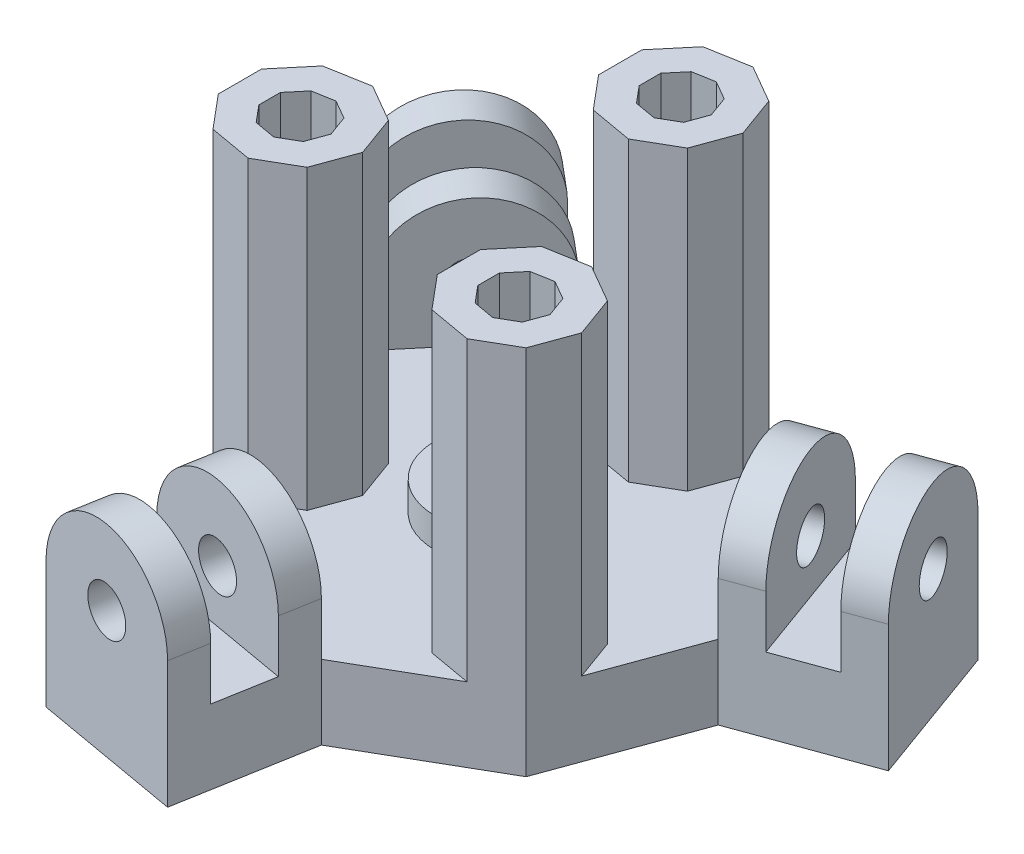
SolidWorks part; units mm, degrees
ref_plane "Front Plane" through (0, 0, 0) normal (0, 0, 1) x (1, 0, 0)
ref_plane "Top Plane" through (0, 0, 0) normal (0, 1, 0) x (1, 0, 0)
ref_plane "Right Plane" through (0, 0, 0) normal (1, 0, 0) x (0, 0, -1)
sketch "Sketch1" plane through (0, 0, 0) normal (0, 1, 0) x (1, 0, 0)
  line L0 (-17.5976, -6.405) -> (-9.3635, -16.2181)
  line L1 (14.3457, -12.0375) -> (18.727, 0)
  line L2 (18.727, 0) -> (14.3457, 12.0375)
  line L3 (14.3457, 12.0375) -> (3.2519, 18.4425)
  line L4 (3.2519, 18.4425) -> (-9.3635, 16.2181)
  line L5 (-9.3635, 16.2181) -> (-17.5976, 6.405)
  line L6 (-17.5976, 6.405) -> (-17.5976, -6.405)
  line L7 (-9.3635, -16.2181) -> (3.2519, -18.4425)
  line L8 (3.2519, -18.4425) -> (14.3457, -12.0375)
  line L9 (14.3457, 12.0375) -> (18.727, 0)
  line L10 (14.3457, 12.0375) -> (25.0112, 15.9194)
  line L11 (18.727, 0) -> (29.3925, 3.8819)
  line L12 (25.0112, 15.9194) -> (29.3925, 3.8819)
  line L13 (3.2519, -18.4425) -> (-9.3635, -16.2181)
  line L14 (3.2519, -18.4425) -> (1.281, -29.6201)
  line L15 (-9.3635, -16.2181) -> (-11.3344, -27.3956)
  line L16 (1.281, -29.6201) -> (-11.3344, -27.3956)
  line L17 (-17.5976, 6.405) -> (-9.3635, 16.2181)
  line L18 (-17.5976, 6.405) -> (-26.2922, 13.7007)
  line L19 (-9.3635, 16.2181) -> (-18.0581, 23.5137)
  line L20 (-26.2922, 13.7007) -> (-18.0581, 23.5137)
  circle A0 centre (0, 0) radius 17.5976 construction
  circle A1 centre (0, 0) radius 4.1
  dimension "D1" = 35.1953
  dimension "D2" = 8.2
  dimension "D3" = 11.35
extrude "Boss-Extrude1" add sketch "Sketch1" along normal blind 6.35 contours L16 L14 L7 L15 | L7 L8 L1 L2 L3 L4 L5 L6 L0 A1 | L12 L10 L2 L11 | L20 L18 L5 L19 region at (-17.08, 0, 0) region at (-4.0413, 0, 22.9191) region at (-17.8279, 0, -14.9594) region at (21.8691, 0, -7.9597)
ref_plane "Plane1" through (-5.0267, 0, 28.5079) normal (0.1736, 0, -0.9848) x (-0.9848, 0, -0.1736)
sketch "Sketch4" plane through (-5.0267, 0, 28.5079) normal (0.1736, 0, -0.9848) x (-0.9848, 0, -0.1736)
  line L0 (-6.405, 6.35) -> (-6.405, 10.85)
  line L1 (6.405, 6.35) -> (6.405, 10.85)
  line L2 (-6.405, 6.35) -> (6.405, 6.35)
  arc A0 (6.405, 10.85) -> (-6.405, 10.85) centre (0, 10.85) ccw
  circle A1 centre (0, 10.85) radius 2
  dimension "D2" = 4
  dimension "D1" = 4.5
extrude "Boss-Extrude2" add sketch "Sketch4" along normal blind 3.18
ref_plane "Plane2" through (-3.0558, 0, 17.3303) normal (0.1736, 0, -0.9848) x (-0.9848, 0, -0.1736)
sketch "Sketch6" plane through (-3.0558, 0, 17.3303) normal (0.1736, 0, -0.9848) x (-0.9848, 0, -0.1736)
  line L0 (-6.405, 6.35) -> (-6.405, 10.85)
  line L1 (6.405, 6.35) -> (6.405, 10.85)
  line L2 (-6.405, 6.35) -> (6.405, 6.35)
  arc A0 (6.405, 10.85) -> (-6.405, 10.85) centre (0, 10.85) ccw
  circle A1 centre (0, 10.85) radius 2
  dimension "D2" = 4
  dimension "D1" = 4.5
extrude "Boss-Extrude4" add sketch "Sketch6" against normal blind 3.175
ref_plane "Plane3" through (27.2019, 0, -9.9007) normal (-0.9397, 0, 0.342) x (0.342, 0, 0.9397)
sketch "Sketch8" plane through (27.2019, 0, -9.9007) normal (-0.9397, 0, 0.342) x (0.342, 0, 0.9397)
  line L0 (-6.405, 10.85) -> (-6.405, 6.35)
  line L1 (-6.405, 6.35) -> (6.405, 6.35)
  line L2 (6.405, 6.35) -> (6.405, 10.85)
  arc A0 (6.405, 10.85) -> (-6.405, 10.85) centre (0, 10.85) ccw
  circle A1 centre (0, 10.85) radius 2
  dimension "D2" = 4
  dimension "D1" = 4.5
extrude "Boss-Extrude5" add sketch "Sketch8" along normal blind 3.175
ref_plane "Plane4" through (16.5364, 0, -6.0187) normal (-0.9397, 0, 0.342) x (0.342, 0, 0.9397)
sketch "Sketch9" plane through (16.5364, 0, -6.0187) normal (-0.9397, 0, 0.342) x (0.342, 0, 0.9397)
  line L0 (-6.405, 6.35) -> (-6.405, 10.85)
  line L1 (-6.405, 6.35) -> (6.405, 6.35)
  line L2 (6.405, 6.35) -> (6.405, 10.85)
  arc A0 (-6.405, 10.85) -> (6.405, 10.85) centre (0, 10.85) cw
  circle A1 centre (0, 10.85) radius 2
  dimension "D2" = 4
  dimension "D1" = 4.5
extrude "Boss-Extrude6" add sketch "Sketch9" against normal blind 3.175
ref_plane "Plane5" through (-22.1752, 0, -18.6072) normal (0.766, 0, 0.6428) x (0.6428, 0, -0.766)
sketch "Sketch10" plane through (-22.1752, 0, -18.6072) normal (0.766, 0, 0.6428) x (0.6428, 0, -0.766)
  line L0 (-6.405, 10.85) -> (-6.405, 6.35)
  line L1 (-6.405, 6.35) -> (6.405, 6.35)
  line L2 (6.405, 6.35) -> (6.405, 10.85)
  arc A0 (6.405, 10.85) -> (-6.405, 10.85) centre (0, 10.85) ccw
  circle A1 centre (0, 10.85) radius 2
  dimension "D2" = 4
  dimension "D1" = 4.5
extrude "Boss-Extrude7" add sketch "Sketch10" along normal blind 3.175
ref_plane "Plane6" through (-13.4806, 0, -11.3115) normal (0.766, 0, 0.6428) x (0.6428, 0, -0.766)
sketch "Sketch11" plane through (-13.4806, 0, -11.3115) normal (0.766, 0, 0.6428) x (0.6428, 0, -0.766)
  line L0 (-6.405, 10.85) -> (-6.405, 6.35)
  line L1 (-6.405, 6.35) -> (6.405, 6.35)
  line L2 (6.405, 6.35) -> (6.405, 10.85)
  arc A0 (6.405, 10.85) -> (-6.405, 10.85) centre (0, 10.85) ccw
  circle A1 centre (0, 10.85) radius 2
  dimension "D2" = 4
  dimension "D1" = 4.5
extrude "Boss-Extrude8" add sketch "Sketch11" against normal blind 3.175
ref_plane "Plane7" through (0, 6.35, 0) normal (0, 1, 0) x (1, 0, 0)
sketch "Sketch12" plane through (0, 6.35, 0) normal (0, 1, 0) x (1, 0, 0)
  line L9 (14.3457, -12.0375) -> (18.727, 0) construction
  line L29 (14.3457, -12.0375) -> (15.6105, -8.5626)
  line L38 (15.6105, -8.5626) -> (14.3457, -5.0876)
  line L48 (6.4544, 9.6437) -> (7.7192, 13.1186)
  line L49 (3.2519, 18.4425) -> (-0.3898, 17.8004)
  line L50 (-0.3898, 17.8004) -> (-2.7668, 14.9676)
  line L51 (-2.7668, 14.9676) -> (-2.7668, 11.2696)
  line L52 (-2.7668, 11.2696) -> (-0.3898, 8.4369)
  line L53 (-0.3898, 8.4369) -> (3.2519, 7.7947)
  line L54 (3.2519, 7.7947) -> (6.4544, 9.6437)
  line L55 (7.7192, 13.1186) -> (6.4544, 16.5935)
  line L56 (6.4544, 16.5935) -> (3.2519, 18.4425)
  line L57 (14.3457, -5.0876) -> (11.1432, -3.2387)
  line L58 (11.1432, -3.2387) -> (7.5015, -3.8808)
  line L59 (7.5015, -3.8808) -> (5.1245, -6.7136)
  line L60 (5.1245, -6.7136) -> (5.1245, -10.4115)
  line L61 (5.1245, -10.4115) -> (7.5015, -13.2443)
  line L62 (7.5015, -13.2443) -> (11.1432, -13.8865)
  line L63 (11.1432, -13.8865) -> (14.3457, -12.0375)
  line L64 (-17.5976, -6.405) -> (-9.3635, -16.2181) construction
  line L65 (3.2519, -18.4425) -> (14.3457, -12.0375) construction
  line L66 (-17.5976, -6.405) -> (-15.2206, -9.2378)
  line L67 (-15.2206, -9.2378) -> (-11.5789, -9.8799)
  line L68 (-11.5789, -9.8799) -> (-8.3764, -8.031)
  line L69 (-8.3764, -8.031) -> (-7.1116, -4.556)
  line L70 (-7.1116, -4.556) -> (-8.3764, -1.0811)
  line L71 (-8.3764, -1.0811) -> (-11.5789, 0.7678)
  line L72 (-11.5789, 0.7678) -> (-15.2206, 0.1257)
  line L73 (-15.2206, 0.1257) -> (-17.5976, -2.7071)
  line L74 (-17.5976, -2.7071) -> (-17.5976, -6.405)
  line L75 (14.3457, 12.0375) -> (3.2519, 18.4425) construction
  line L76 (-0.2268, 12.1941) -> (0.9617, 10.7777)
  line L77 (4.3838, 11.3812) -> (5.0162, 13.1186)
  line L78 (5.0162, 13.1186) -> (4.3838, 14.8561)
  line L79 (4.3838, 14.8561) -> (2.7825, 15.7806)
  line L80 (2.7825, 15.7806) -> (0.9617, 15.4595)
  line L81 (0.9617, 15.4595) -> (-0.2268, 14.0431)
  line L82 (-0.2268, 14.0431) -> (-0.2268, 12.1941)
  line L83 (0.9617, 10.7777) -> (2.7825, 10.4567)
  line L84 (2.7825, 10.4567) -> (4.3838, 11.3812)
  line L86 (12.2751, -10.3) -> (12.9075, -8.5626)
  line L87 (12.9075, -8.5626) -> (12.2751, -6.8251)
  line L88 (12.2751, -6.8251) -> (10.6738, -5.9006)
  line L89 (10.6738, -5.9006) -> (8.853, -6.2217)
  line L90 (8.853, -6.2217) -> (7.6645, -7.6381)
  line L91 (7.6645, -7.6381) -> (7.6645, -9.4871)
  line L92 (7.6645, -9.4871) -> (8.853, -10.9034)
  line L93 (8.853, -10.9034) -> (10.6738, -11.2245)
  line L94 (10.6738, -11.2245) -> (12.2751, -10.3)
  line L95 (-10.447, -6.2935) -> (-9.8146, -4.556)
  line L96 (-9.8146, -4.556) -> (-10.447, -2.8186)
  line L97 (-10.447, -2.8186) -> (-12.0483, -1.8941)
  line L98 (-12.0483, -1.8941) -> (-13.8691, -2.2152)
  line L99 (-13.8691, -2.2152) -> (-15.0576, -3.6316)
  line L100 (-15.0576, -3.6316) -> (-15.0576, -5.4805)
  line L101 (-15.0576, -5.4805) -> (-13.8691, -6.8969)
  line L102 (-13.8691, -6.8969) -> (-12.0483, -7.218)
  line L103 (-12.0483, -7.218) -> (-10.447, -6.2935)
  circle A0 centre (2.3132, 13.1186) radius 5.08 construction
  circle A1 centre (10.2045, -8.5626) radius 5.08 construction
  circle A2 centre (-12.5176, -4.556) radius 5.08 construction
  circle A3 centre (2.3132, 13.1186) radius 2.54 construction
  circle A4 centre (10.2045, -8.5626) radius 2.54 construction
  circle A5 centre (-12.5176, -4.556) radius 2.54 construction
  dimension "D1" = 10.16
  dimension "D2" = 2.54
  dimension "D3" = 2.54
  dimension "D4" = 2.54
extrude "Boss-Extrude9" add sketch "Sketch12" along normal blind 25.4
ref_plane "Plane8" through (0, 6.35, 0) normal (0, 1, 0) x (1, 0, 0)
sketch "Sketch15" plane through (0, 6.35, 0) normal (0, 1, 0) x (1, 0, 0)
  circle A0 centre (0, 0) radius 4
  circle A2 centre (0, 0) radius 5.5
  dimension "D1" = 8
  dimension "D2" = 11
extrude "Boss-Extrude10" add sketch "Sketch15" along normal blind 2.54
